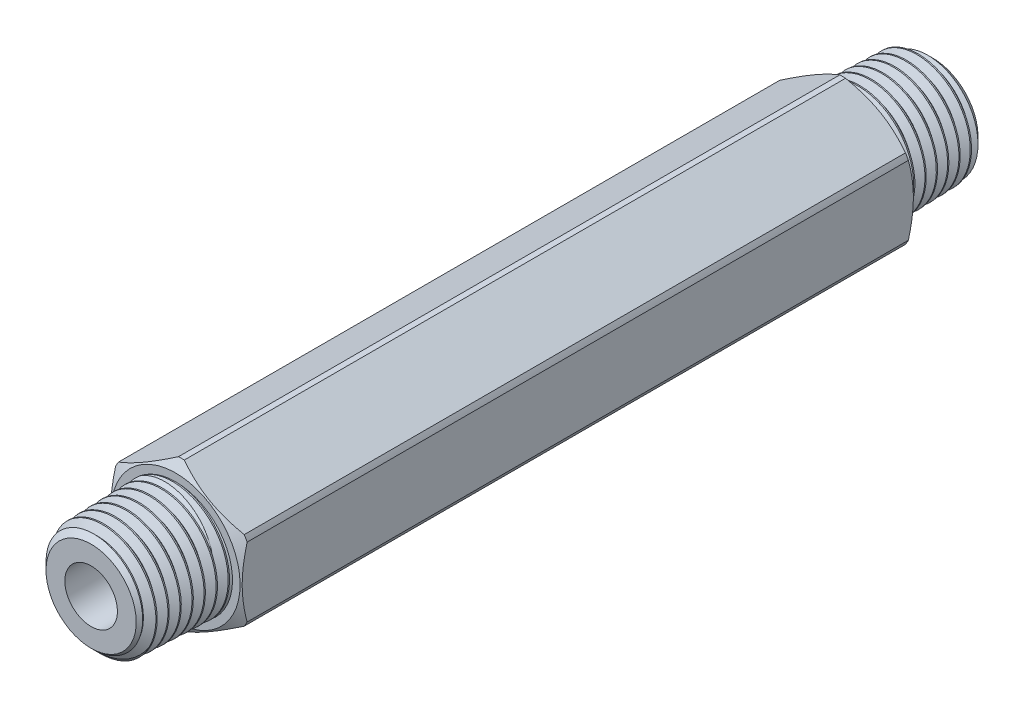
SolidWorks part; units mm, degrees
note: The reader was unsure of these and kept them because the rebuilt part matched: shared geometry of "Sketch9<2>".
material "AISI 316 Annealed Stainless Steel Bar (SS)"
ref_plane "Front Plane" through (0, 0, 0) normal (0, 0, 1) x (1, 0, 0)
ref_plane "Top Plane" through (0, 0, 0) normal (0, 1, 0) x (1, 0, 0)
ref_plane "Right Plane" through (0, 0, 0) normal (1, 0, 0) x (0, 0, -1)
sketch "Sketch1" plane through (0, 0, 0) normal (1, 0, 0) x (0, 0, -1)
  line L0 (-50.8, 0) -> (50.8, 0) construction
  line L1 (0, 7.9375) -> (0, -7.9375) construction
  line L2 (-40.5943, -6.858) -> (-40.5943, 6.858) construction
  line L3 (-45.5332, -6.7042) -> (-45.5332, 6.7042) construction
  line L4 (-50.8, -3.175) -> (-50.8, 3.175) construction
  line L5 (-40.5943, 6.858) -> (-50.8, 6.5402) construction
  point P4 (0, 0)
  point P8 (-42.0054, 6.8141)
  point P11 (-40.5943, 0)
  point P16 (-45.5332, 0)
  dimension "Pipe Size" = 6.35
  dimension "Length" = 101.6
  dimension "Thread Pitch" = 1.4111
  dimension "D1" = 1.783
  dimension "Thread Length" = 10.2057
  dimension "Thread Diameter" = 13.716
  dimension "Hex Width" = 15.875
  dimension "D2" = 4.9389
sketch "Sketch2" plane through (0, 0, 0) normal (1, 0, 0) x (0, 0, -1)
  line L0 (-50.8, 3.175) -> (50.8, 3.175)
  line L1 (-50.8, 3.175) -> (-50.8, 5.4465)
  line L2 (-50.8, 5.4465) -> (-49.6711, 6.5754)
  line L3 (-40.5943, 6.858) -> (-50.8, 6.5402) construction
  line L4 (-49.6711, 6.5754) -> (-40.5943, 6.858)
  line L5 (-40.5943, 6.858) -> (-40.5943, 7.9375)
  line L6 (-40.5943, 7.9375) -> (40.5943, 7.9375)
  line L7 (40.5943, 7.9375) -> (40.5943, 6.858)
  line L8 (40.5943, 6.858) -> (49.6711, 6.5754)
  line L9 (49.6711, 6.5754) -> (50.8, 5.4465)
  line L10 (50.8, 5.4465) -> (50.8, 3.175)
  line L11 (-50.8, 0) -> (50.8, 0) construction
  line L12 (-50.8, -3.175) -> (-50.8, 3.175) construction
  dimension "D1" = 1.1289
  dimension "D2" = 45
  dimension "D3" = 45
revolve "Revolve1" add sketch "Sketch2" angle 360 about L11
sketch "Sketch3" plane through (0, 0, 40.5943) normal (0, 0, 1) x (1, 0, 0)
  line L1 (0, 9.1654) -> (-7.9375, 4.5827)
  line L2 (-7.9375, 4.5827) -> (-7.9375, -4.5827)
  line L3 (-7.9375, -4.5827) -> (0, -9.1654)
  line L4 (0, -9.1654) -> (7.9375, -4.5827)
  line L5 (7.9375, -4.5827) -> (7.9375, 4.5827)
  line L6 (7.9375, 4.5827) -> (0, 9.1654)
  circle A0 centre (0, 0) radius 7.9375 construction
  circle A1 centre (0, 0) radius 7.9375 construction
  circle A2 centre (0, 0) radius 6.858 construction
  circle A3 centre (0, 0) radius 6.858
extrude "Boss-Extrude1" add sketch "Sketch3" against normal up to surface (81.1886 mm away) up to face at (0, -7.9375, -40.5943)
sketch "Sketch4" plane through (0, 0, 0) normal (1, 0, 0) x (0, 0, -1)
  line L0 (-40.5943, 7.7788) -> (-40.5943, 9.1654)
  line L1 (-40.5943, 9.1654) -> (40.5943, 9.1654)
  line L2 (40.5943, 9.1654) -> (40.5943, 7.7788)
  line L3 (40.5943, 7.7788) -> (39.9069, 8.9694)
  line L4 (39.9069, 8.9694) -> (-39.9069, 8.9694)
  line L5 (-39.9069, 8.9694) -> (-40.5943, 7.7788)
  line L6 (-50.8, 0) -> (50.8, 0) construction
  dimension "D1" = 15.5575
  dimension "D2" = 17.9387
  dimension "D3" = 30
revolve "Cut-Revolve1" cut sketch "Sketch4" angle 360 about L6
sketch "Sketch5" plane through (0, 0, 0) normal (1, 0, 0) x (0, 0, -1)
  line L0 (-40.5943, -7.9375) -> (-40.5943, 7.9375)
  line L2 (40.5943, -7.9375) -> (40.5943, 7.9375)
  line L4 (-40.5943, 7.9375) -> (40.5943, 7.9375) construction
  point P4 (-40.5943, 0)
  point P8 (40.5943, 0)
split "Split1" trim tools "Sketch5" bodies to split 106 resulting bodies 107 108 109
sketch "Sketch6" plane through (0, 0, 40.5943) normal (0, 0, 1) x (1, 0, 0)
  circle A0 centre (0, 0) radius 6.858 construction
  circle A1 centre (0, 0) radius 6.858
curve "Helix/Spiral1"
sketch "Sketch7" plane through (0, 0, 0) normal (1, 0, 0) x (0, 0, -1)
  line L0 (-40.6825, 7.0108) -> (-39.2714, 7.0108) construction
  line L1 (-39.2714, 7.0108) -> (-39.9769, 5.7887) construction
  line L2 (-39.9769, 5.7887) -> (-40.6825, 7.0108) construction
  line L3 (-40.5943, 6.858) -> (-39.3596, 6.858) construction
  line L4 (-40.0651, 5.9415) -> (-39.8887, 5.9415) construction
  line L5 (-39.9769, 6.858) -> (-39.9769, 7.0108) construction
  line L6 (-39.9769, 5.9415) -> (-39.9769, 5.7887) construction
  line L7 (-40.6384, 6.9344) -> (-39.3155, 6.9344) construction
  point P13 (-39.9769, 6.9344)
  dimension "D1" = 1.4111
  dimension "D2" = 0.1764
sketch "Sketch8" plane through (0, 0, 0) normal (1, 0, 0) x (0, 0, -1)
  line L0 (-40.6384, 6.9344) -> (-39.3155, 6.9344)
  line L1 (-39.3155, 6.9344) -> (-39.8887, 5.9415)
  line L2 (-39.8887, 5.9415) -> (-40.0651, 5.9415)
  line L3 (-40.0651, 5.9415) -> (-40.6384, 6.9344)
sweep "Cut-Sweep1" cut profiles "Sketch8" path "Helix/Spiral1"
delete or keep bodies "Body-Delete/Keep 1" type delete bodies bodies 107
pattern_circular "CirPattern1" count 2 over 360 about axis through (0, 7.9375, 0) along (0, -1, 0) of bodies 110
sketch "Sketch9" plane through (0, 0, 40.5943) normal (0, 0, 1) x (1, 0, 0)
  circle A0 centre (0, 0) radius 6.858
  circle A1 centre (0, 0) radius 3.175 construction
  circle A2 centre (0, 0) radius 3.175
extrude "Boss-Extrude2" add sketch "Sketch9" along normal through all draft 45
extrude "Boss-Extrude3" add sketch "Sketch9<2>" against normal through all draft 45 from surface at -81.1886 starting at face at (-3.175, 0, -40.5943)
sketch "Sketch9<2>" plane through (0, 0, 40.5943) normal (0, 0, 1) x (1, 0, 0) same geometry as "Sketch9"
equation "\"D1@Sketch2\"=\"Thread Pitch@Sketch1\"*.8"
equation "\"D1@Sketch4\"=\"Hex Width@Sketch1\"*.98"
equation "\"D2@Sketch4\"=\"Hex Width@Sketch1\"*1.13"
equation "\"D3@Helix/Spiral1\"=\"Thread Length@Sketch1\"+\"Thread Pitch@Sketch1\""
equation "\"D4@Helix/Spiral1\"=\"Thread Pitch@Sketch1\""
equation "\"D2@Sketch7\"=\"D1@Sketch7\"/8"
equation "\"D1@Sketch7\"=\"Thread Pitch@Sketch1\""
equation "\"D2@Sketch1\"=\"Thread Pitch@Sketch1\"*3.5"
